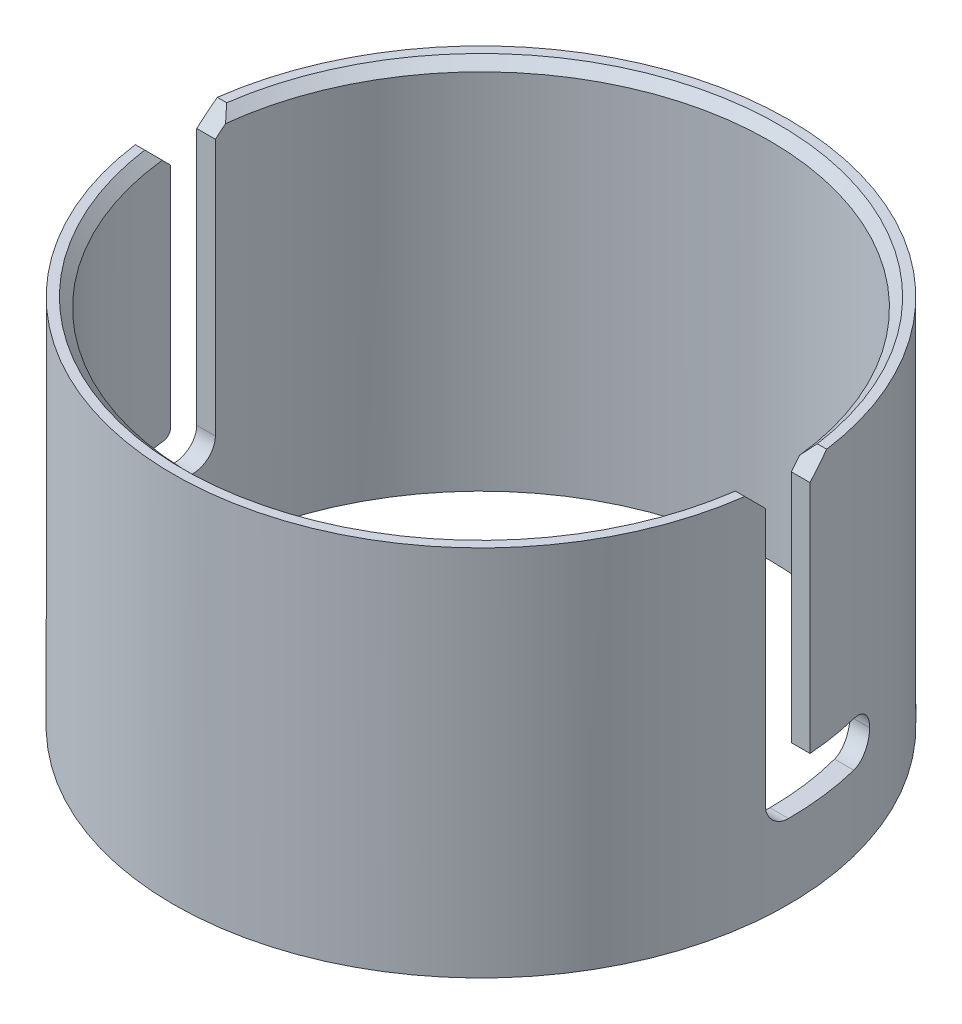
SolidWorks part; units mm, degrees
material "Plain Carbon Steel"
ref_plane "Front Plane" through (0, 0, 0) normal (0, 0, 1) x (1, 0, 0)
ref_plane "Top Plane" through (0, 0, 0) normal (0, 1, 0) x (1, 0, 0)
ref_plane "Right Plane" through (0, 0, 0) normal (1, 0, 0) x (0, 0, -1)
sketch "Sketch2" plane through (0, 0, 0) normal (1, 0, 0) x (0, 0, -1)
  line L0 (-77.55, 0) -> (-82.55, 0)
  line L1 (-82.55, 0) -> (-82.55, 100)
  line L2 (-82.55, 100) -> (-77.55, 100)
  line L5 (-77.55, 100) -> (-77.55, 0)
  dimension "D1" = 82.55
  dimension "D2" = 100
  dimension "D3" = 5
ref_axis "Axis1" through (0, -3.6075, 0) along (0, 1, 0)
revolve "Revolve1" add sketch "Sketch2" angle 360 about axis through (0, -3.6075, 0) along (0, 1, 0)
sketch "Sketch3" plane through (0, 0, 0) normal (1, 0, 0) x (0, 0, -1)
  line L0 (-6, 100) -> (6, 100)
  line L1 (82.55, 100) -> (-82.55, 100) construction
  line L2 (6, 100) -> (6, 20)
  line L3 (6, 20) -> (-26, 20)
  line L4 (-26, 20) -> (-26, 32)
  line L5 (-26, 32) -> (-6, 32)
  line L6 (-6, 32) -> (-6, 100)
  line L7 (0, -3.6075) -> (0, 75.7575) construction
  line L8 (0, 0) -> (0, 47.5309) construction
  line L9 (-82.55, 0) -> (82.55, 0) construction
  dimension "D1" = 20
  dimension "D2" = 12
  dimension "D3" = 12
  dimension "D4" = 20
extrude "Cut-Extrude1" cut sketch "Sketch3" against normal through all
fillet "Fillet1" radius 6 1 edges at (-79.8246, 20, -6)
chamfer "Chamfer1" distance 5 angle 45 2 edges at (-79.8246, 100, 6) (-79.8246, 100, -6)
fillet "Fillet3" radius 6 2 edges at (-75.7051, 32, 26) (-75.7051, 20, 26)
pattern_circular "CirPattern1" count 2 over 360 about axis through (0, -3.6075, 0) along (0, 1, 0) of "Fillet3", "Chamfer1", "Fillet1", "Cut-Extrude1"
chamfer "Chamfer2" distance 2.5 angle 45 2 edges at (0, 100, -77.55) (0, 100, 77.55)
fillet "Fillet4" radius 2 1 edges at (-79.8246, 32, 6)
equation "\"TubeDiameter\" = 6.500in"
equation "\"D1@Sketch2\"=\"TubeDiameter\"/2"
